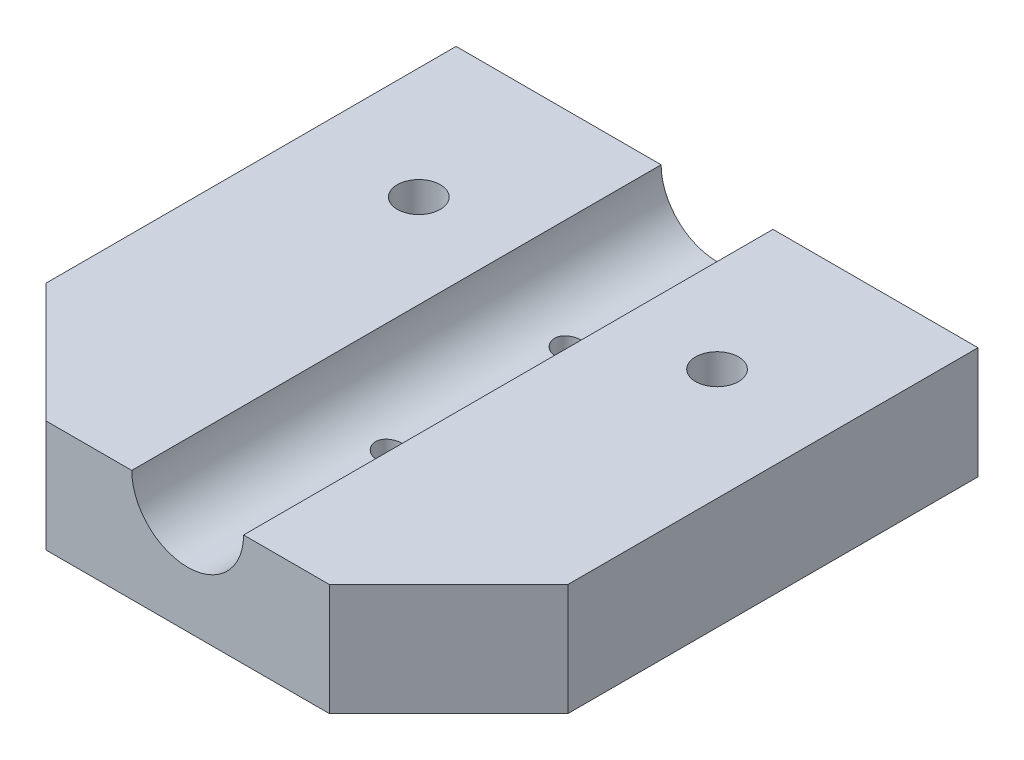
SolidWorks part; units mm, degrees
material "Nylon 6/10"
ref_plane "Front Plane" through (0, 0, 0) normal (0, 0, 1) x (1, 0, 0)
ref_plane "Top Plane" through (0, 0, 0) normal (0, 1, 0) x (1, 0, 0)
ref_plane "Right Plane" through (0, 0, 0) normal (1, 0, 0) x (0, 0, -1)
sketch "Sketch1" plane through (0, 0, 0) normal (0, 1, 0) x (1, 0, 0)
  line L1 (-22.225, -22.5425) -> (22.225, -22.5425)
  line L2 (-22.225, -22.5425) -> (-22.225, 22.5425)
  line L3 (-22.225, 22.5425) -> (22.225, 22.5425)
  line L4 (22.225, -22.5425) -> (22.225, 22.5425)
  line L5 (-22.225, -22.5425) -> (22.225, 22.5425) construction
  line L6 (-22.225, 22.5425) -> (22.225, -22.5425) construction
  point P0 (0, 0)
  dimension "D1" = 45.085
  dimension "D2" = 44.45
extrude "Boss-Extrude1" add sketch "Sketch1" along normal blind 9.525
sketch "Sketch4" plane through (0, 0, 22.5425) normal (0, 0, 1) x (1, 0, 0)
  line L0 (-22.225, 9.525) -> (22.225, 9.525) construction
  circle A0 centre (0, 9.525) radius 4.7625
  dimension "D1" = 9.525
extrude "Cut-Extrude1" cut sketch "Sketch4" against normal through all
hole_wizard "MotorHoles" positions "Sketch3" profile "Sketch2" tap size "#4-40" standard "ANSI Inch"
sketch "Sketch3" plane through (0, 0, 0) normal (0, -1, 0) x (-1, 0, 0)
  line L0 (22.225, -22.5425) -> (-22.225, -22.5425) construction
  line L2 (0, 0) -> (0, -31.1437) construction
  point P0 (-5.715, -19.3675)
  point P2 (5.715, -19.3675)
  point P15 (13.081, 19.6469)
  point P17 (-13.081, 19.6469)
  dimension "D1" = 3.175
  dimension "D2" = 11.43
  dimension "D3" = 39.0144
  dimension "D4" = 7.366
  dimension "D5" = 7.366
cosmetic thread "Hole Thread1" parameters "D1"=5.588, "D2"=2.8448
cosmetic thread "Hole Thread2" parameters "D1"=5.588, "D2"=2.8448
sketch "Sketch2" plane through (5.715, 0, 19.3675) normal (1, 0, 0) x (0, 0, -1)
  line L0 (0, 0) -> (0, 7.0292)
  line L1 (0, 7.0292) -> (1.1303, 6.35)
  line L2 (1.1303, 6.35) -> (1.1303, 0)
  line L5 (1.1303, 0) -> (0, 0)
  line L10 (0, 7.0292) -> (-1.1303, 6.35) construction
  line L11 (0, -6.35) -> (0, 107.95) construction
  dimension "Tap Drill Dia." = 2.2606
  dimension "Tap Drill Depth" = 6.35
  dimension "Drill Angle" = 118
cosmetic thread "Hole Thread5" parameters "D1"=5.588, "D2"=2.8448
cosmetic thread "Hole Thread6" parameters "D1"=5.588, "D2"=2.8448
hole_wizard "CBORE for #6 Socket Head Cap Screw1" positions "Sketch6" profile "Sketch5" counterbore size "#6" standard "ANSI Inch" end condition through all
sketch "Sketch6" plane through (0, 0, 0) normal (0, -1, 0) x (-1, 0, 0)
  line L0 (0, 0) -> (0, 20.3228) construction
  line L2 (-22.225, 22.5425) -> (22.225, 22.5425) construction
  point P0 (-12.7, 9.8425)
  point P2 (12.7, 9.8425)
  dimension "D1" = 25.4
  dimension "D2" = 12.7
sketch "Sketch5" plane through (12.7, 0, -9.8425) normal (1, 0, 0) x (0, 0, -1)
  line L0 (0, 0) -> (0, 9.525)
  line L1 (0, 9.525) -> (1.8288, 9.525)
  line L3 (1.8288, 9.525) -> (1.8288, 3.5052)
  line L4 (3.5725, 3.5052) -> (1.8288, 3.5052)
  line L5 (3.5725, 3.5052) -> (3.5725, 0.635)
  line L6 (3.5725, 0.635) -> (4.2075, 0)
  line L7 (4.2075, 0) -> (0, 0)
  line L8 (-3.5725, 0.635) -> (-4.2075, 0) construction
  line L11 (0, -6.35) -> (0, 107.95) construction
  dimension "Thru Hole Dia." = 3.6576
  dimension "Thru Hole Depth" = 9.525
  dimension "C'Bore Dia." = 7.145
  dimension "C'Bore Depth" = 3.5052
  dimension "Near C'Sink Dia." = 8.415
  dimension "Near C'Sink Angle" = 90
chamfer "Chamfer1" distance 10.16 angle 45 2 edges at (22.225, 4.7625, 22.5425) (-22.225, 4.7625, 22.5425)
hole_wizard "#4-40 Tapped Hole1" positions "Sketch8" profile "Sketch7" tap size "#4-40" standard "ANSI Inch" end condition through all
sketch "Sketch8" plane through (0, 0, 0) normal (0, -1, 0) x (-1, 0, 0)
  line L0 (0, 0) -> (0, 3.4708) construction
  line L2 (-12.7, 9.8425) -> (12.7, 9.8425) construction
  point P0 (0, 9.8425)
  point P2 (0, -5.3975)
  dimension "D1" = 15.24
sketch "Sketch7" plane through (0, 0, -9.8425) normal (1, 0, 0) x (0, 0, -1)
  line L0 (0, 0) -> (0, 9.525)
  line L1 (0, 9.525) -> (1.1303, 9.525)
  line L2 (1.1303, 9.525) -> (1.1303, 0)
  line L5 (1.1303, 0) -> (0, 0)
  line L11 (0, -6.35) -> (0, 107.95) construction
  dimension "Thru Tap Drill Dia." = 2.2606
  dimension "Thru Tap Drill Depth" = 9.525
cosmetic thread "Hole Thread3" parameters "D2"=2.8448
cosmetic thread "Hole Thread4" parameters "D2"=2.8448
chamfer "Chamfer3" [suppressed] distance 5.08 angle 45
